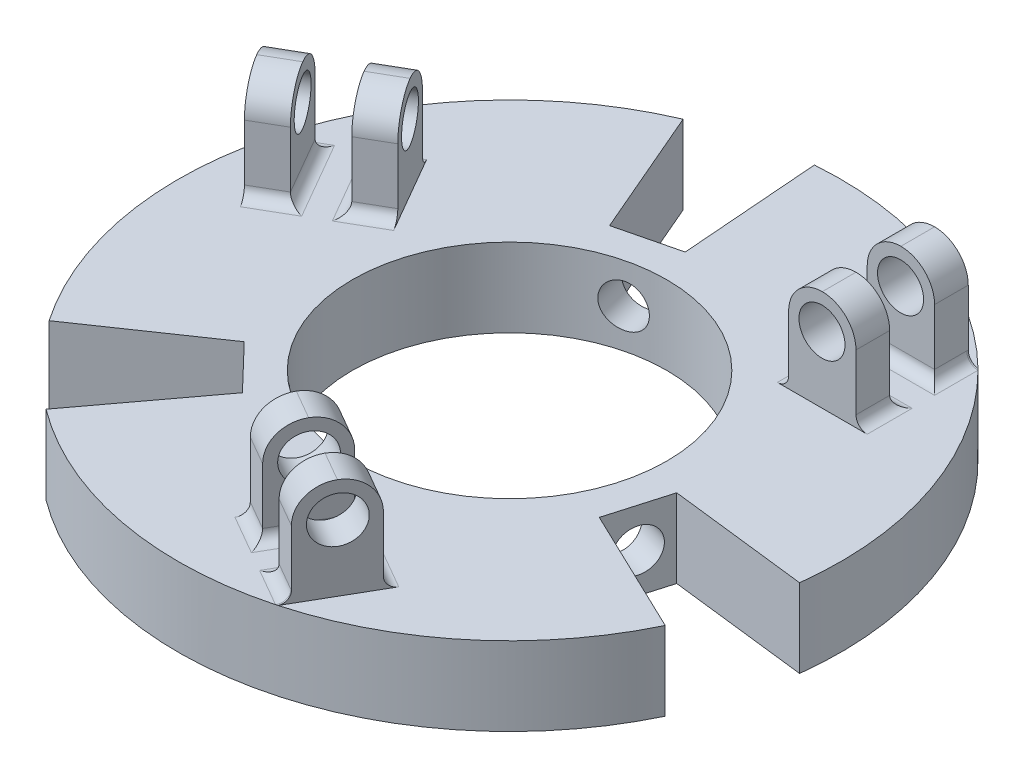
SolidWorks part; units mm, degrees
ref_plane "Front Plane" through (0, 0, 0) normal (0, 0, 1) x (1, 0, 0)
ref_plane "Top Plane" through (0, 0, 0) normal (0, 1, 0) x (1, 0, 0)
ref_plane "Right Plane" through (0, 0, 0) normal (1, 0, 0) x (0, 0, -1)
sketch "Sketch1" plane through (0, 0, 0) normal (0, 1, 0) x (1, 0, 0)
  line L0 (0, 0) -> (0, 14) construction
  line L2 (-1.3063, 16.9497) -> (-1.9979, 25.9231)
  line L4 (-6.7119, 15.6189) -> (-10.2652, 23.8878)
  line L10 (-6.7119, 15.6189) -> (-1.3063, 16.9497)
  line L22 (-10.2652, 23.8878) -> (-11.6471, 27.1034)
  line L23 (-1.9979, 25.9231) -> (-2.2668, 29.4128)
  line L24 (16.8823, -1.9968) -> (25.82, -3.0539)
  line L25 (25.82, -3.0539) -> (29.2958, -3.465)
  line L26 (16.8823, -1.9968) -> (15.332, -7.3436)
  line L27 (15.332, -7.3436) -> (23.449, -11.2314)
  line L28 (23.449, -11.2314) -> (26.6056, -12.7433)
  line L29 (-10.1704, -13.6221) -> (-15.5548, -20.8338)
  line L30 (-15.5548, -20.8338) -> (-17.6487, -23.6384)
  line L31 (-10.1704, -13.6221) -> (-14.0258, -9.6061)
  line L32 (-14.0258, -9.6061) -> (-21.4512, -14.6918)
  line L33 (-21.4512, -14.6918) -> (-24.3388, -16.6695)
  circle A1 centre (0, 0) radius 14
  arc A7 (-11.6471, 27.1034) -> (-24.3388, -16.6695) centre (0, 0) ccw
  arc A16 (-17.6487, -23.6384) -> (26.6056, -12.7433) centre (0, 0) ccw
  arc A17 (29.2958, -3.465) -> (-2.2668, 29.4128) centre (0, 0) ccw
  point P4 (0, 22.2656)
  point P20 (0, 0)
  point P21 (0, 0)
  point P27 (0, 0)
  point P32 (0, 0)
  dimension "D1" = 59
  dimension "D2" = 28
  dimension "D3" = 3
extrude "Boss-Extrude1" add sketch "Sketch1" along normal blind 7
sketch "Sketch3" plane through (0, 7, 0) normal (0, 1, 0) x (1, 0, 0)
  line L0 (0, 21.4129) -> (0, 10.5871) construction
  line L6 (13.8521, 14) -> (19.8521, 14)
  line L11 (13.8521, 14) -> (13.8521, 11)
  line L12 (13.8521, 11) -> (19.8521, 11)
  line L13 (19.8521, 14) -> (19.8521, 11)
  line L14 (13.8521, 14) -> (19.8521, 11) construction
  line L15 (13.8521, 11) -> (19.8521, 14) construction
  line L16 (13.8521, 18) -> (19.8521, 18)
  line L17 (13.8521, 18) -> (13.8521, 21)
  line L18 (13.8521, 21) -> (19.8521, 21)
  line L19 (19.8521, 18) -> (19.8521, 21)
  line L20 (13.8521, 18) -> (19.8521, 21) construction
  line L21 (13.8521, 21) -> (19.8521, 18) construction
  point P0 (16.8521, 12.5)
  point P5 (16.8521, 19.5)
  dimension "D1" = 3
  dimension "D2" = 6
  dimension "D3" = 3
  dimension "D4" = 6
  dimension "D5" = 4
  dimension "D6" = 18
extrude "Boss-Extrude2" add sketch "Sketch3" along normal blind 9
fillet "Fillet1" radius 3 4 edges at (19.8521, 16, -12.5) (13.8521, 16, -12.5) (13.8521, 16, -19.5) (19.8521, 16, -19.5)
fillet "Fillet2" radius 1 6 edges at (16.8521, 7, -14) (16.8521, 7, -18) (19.8521, 7, -12.5) (13.8521, 7, -12.5) (13.8521, 7, -19.5) (19.8521, 7, -19.5)
sketch "Sketch5" plane through (0, 0, -11) normal (0, 0, 1) x (1, 0, 0)
  circle A0 centre (16.8231, 12.9) radius 2.05
  dimension "D1" = 4.1
  dimension "D2" = 3.1
extrude "Cut-Extrude2" cut sketch "Sketch5" against normal through all both and the other way through all
pattern_circular "CirPattern2" count 3 over 360 about axis through (0, 7, 0) along (0, -1, 0) of "Boss-Extrude2", "Fillet1", "Fillet2", "Cut-Extrude2"
sketch "Sketch6" plane through (-4.0091, 0, -16.2843) normal (-0.2391, 0, -0.971) x (-0.971, 0, 0.2391)
  line L0 (0, 0) -> (0, 7) construction
  line L1 (25.8485, 7) -> (4.8302, 7) construction
  circle A0 centre (0, 3.5) radius 1.9
  dimension "D1" = 3.8
extrude "Cut-Extrude3" cut sketch "Sketch6" against normal blind 3
pattern_circular "CirPattern3" count 3 over 360 about axis through (0, 7, 0) along (0, 1, 0) of "Cut-Extrude3"
